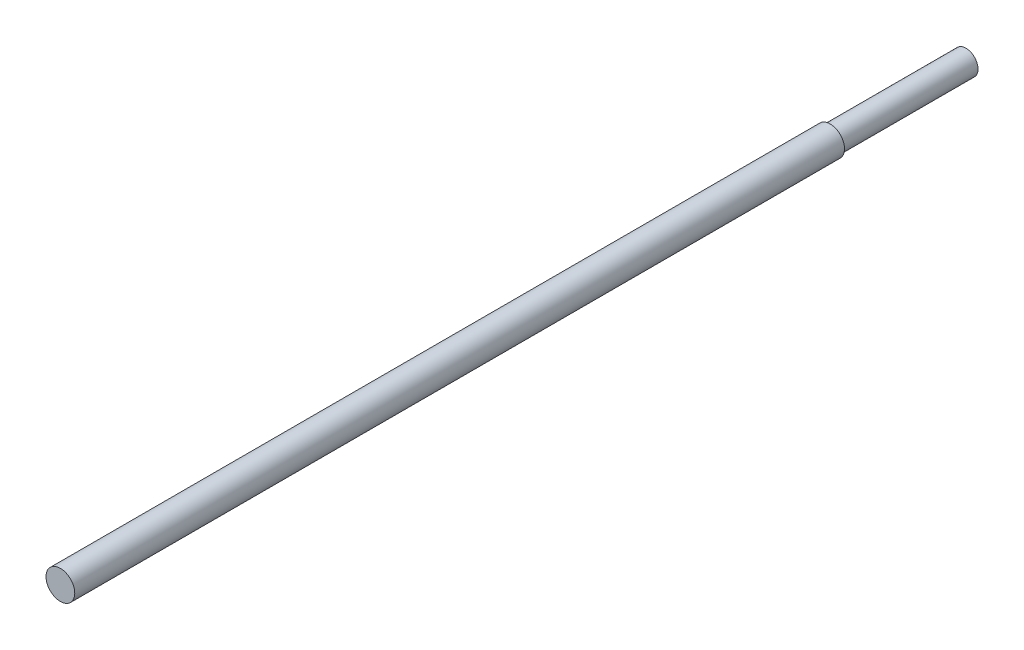
SolidWorks part; units mm, degrees
ref_plane "Front Plane" through (0, 0, 0) normal (0, 0, 1) x (1, 0, 0)
ref_plane "Top Plane" through (0, 0, 0) normal (0, 1, 0) x (1, 0, 0)
ref_plane "Right Plane" through (0, 0, 0) normal (1, 0, 0) x (0, 0, -1)
sketch "Sketch1" plane through (0, 0, 0) normal (0, 0, 1) x (1, 0, 0)
  circle A0 centre (0, 0) radius 4.7625
  dimension "D1" = 9.525
extrude "Boss-Extrude1" add sketch "Sketch1" along normal blind 300
sketch "Sketch3" plane through (0, 0, 0) normal (0, 0, -1) x (-1, 0, 0)
  circle A0 centre (0, 0) radius 4.7625
  circle A1 centre (0, 0) radius 4
  dimension "D1" = 9.525
  dimension "D2" = 8
extrude "Cut-Extrude2" cut sketch "Sketch3" against normal blind 45
